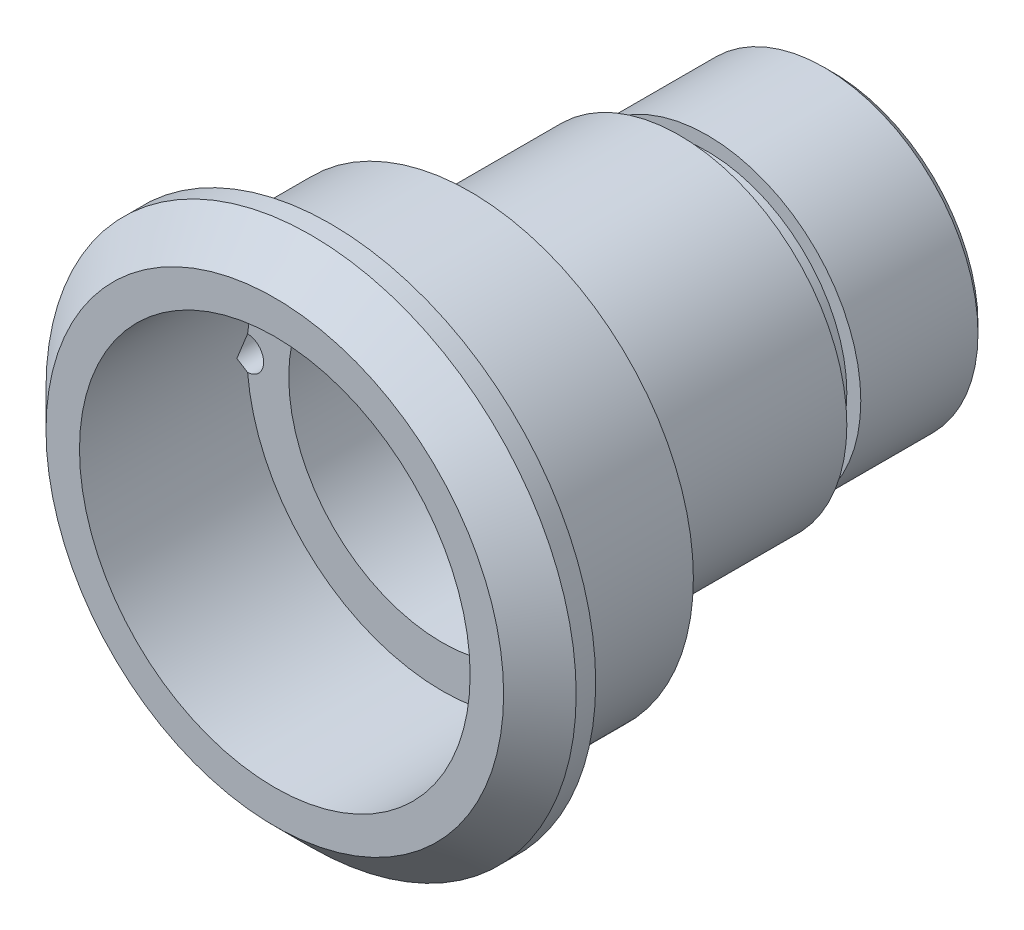
SolidWorks part; units mm, degrees
ref_plane "Front Plane" through (0, 0, 0) normal (0, 0, 1) x (1, 0, 0)
ref_plane "Top Plane" through (0, 0, 0) normal (0, 1, 0) x (1, 0, 0)
ref_plane "Right Plane" through (0, 0, 0) normal (1, 0, 0) x (0, 0, -1)
sketch "Sketch1" plane through (0, 0, 0) normal (0, 0, 1) x (1, 0, 0)
  circle A0 centre (0, 0) radius 9.5
  dimension "D1" = 19
extrude "Boss-Extrude1" add sketch "Sketch1" against normal blind 20
sketch "Sketch2" plane through (0, 0, -20) normal (0, 0, -1) x (-1, 0, 0)
  circle A0 centre (0, 0) radius 8
  dimension "D1" = 16
extrude "Cut-Extrude1" cut sketch "Sketch2" against normal offset from surface (18 mm away) 2 flip side to cut up to face at (9.5, 0, 0)
sketch "Sketch3" plane through (0, 0, -20) normal (0, 0, -1) x (-1, 0, 0)
  circle A0 centre (0, 0) radius 6
  dimension "D1" = 12
extrude "Cut-Extrude2" cut sketch "Sketch3" against normal offset from surface (13 mm away) 5 flip side to cut up to face at (9.5, 0, -2)
sketch "Sketch4" plane through (0, 0, -20) normal (0, 0, -1) x (-1, 0, 0)
  circle A0 centre (0, 0) radius 5.5
  dimension "D1" = 11
extrude "Cut-Extrude3" cut sketch "Sketch4" against normal offset from surface (5.5 mm away) 7.5 flip side to cut up to face at (8, 0, -7)
sketch "Sketch5" plane through (0, 0, 0) normal (1, 0, 0) x (0, 0, -1)
  line L0 (0, 0) -> (20, 0) construction
  line L1 (0, 9.5) -> (0, -9.5) construction
  line L2 (20, -5.5) -> (20, 5.5) construction
  line L4 (14.5, 5.5) -> (15.5, 5.5)
  line L5 (14.5, 5.5) -> (14.5, 5)
  line L6 (14.5, 5) -> (15.5, 5)
  line L7 (15.5, 5.5) -> (15.5, 5)
  dimension "D1" = 10
  dimension "D2" = 1
revolve "Cut-Revolve1" cut sketch "Sketch5" angle 360 about L0
chamfer "Chamfer1" distance 0.3 angle 45 1 edges at (-5.5, 0, -20)
chamfer "Chamfer2" distance 1.3 angle 45 1 edges at (9.5, 0, 0)
sketch "Sketch6" plane through (0, 0, 0) normal (1, 0, 0) x (0, 0, -1)
  line L0 (0, 0) -> (20, 0) construction
  line L1 (20, -5.2) -> (20, 5.2) construction
  line L2 (7, -6.433) -> (6.75, -6)
  line L3 (7, -8) -> (7, 8) construction
  line L4 (7, -6) -> (14.5, -6) construction
  line L5 (6.75, -6) -> (7, -6)
  line L6 (7, -6.433) -> (7, -6)
  dimension "D1" = 60
  dimension "D2" = 0.25
revolve "Cut-Revolve2" cut sketch "Sketch6" angle 360 about L0
sketch "Sketch7" plane through (0, 0, 0) normal (0, 0, 1) x (1, 0, 0)
  circle A0 centre (0, 0) radius 4.05
  dimension "D1" = 8.1
extrude "Cut-Extrude4" cut sketch "Sketch7" against normal through all
sketch "Sketch8" plane through (0, 0, -20) normal (0, 0, -1) x (-1, 0, 0)
  circle A0 centre (0, 0) radius 4.5
  dimension "D1" = 9
extrude "Cut-Extrude5" cut sketch "Sketch8" against normal blind 4.5
sketch "Sketch9" plane through (0, 0, -15.5) normal (0, 0, -1) x (-1, 0, 0)
  circle A0 centre (0, 0) radius 4.45
  dimension "D1" = 8.9
extrude "Cut-Extrude9" cut sketch "Sketch9" against normal offset from surface (0.2 mm away) 8.3 up to face at (6.433, 0, -7)
sketch "Sketch10" plane through (0, 0, 0) normal (0, 0, 1) x (1, 0, 0)
  circle A0 centre (0, 0) radius 7
  dimension "D1" = 14
extrude "Cut-Extrude11" cut sketch "Sketch10" against normal offset from surface (6 mm away) 1 up to face at (6.433, 0, -7)
sketch "Sketch11" plane through (0, 0, -6) normal (0, 0, 1) x (1, 0, 0)
  circle A0 centre (0, 0) radius 5.5
  dimension "D1" = 11
extrude "Cut-Extrude12" cut sketch "Sketch11" against normal offset from surface (5.6 mm away) 4.6 up to face at (6.433, 0, -7) offset beyond the face yes
sketch "Sketch12" plane through (0, 0, -11.6) normal (0, 0, 1) x (1, 0, 0)
  circle A0 centre (0, 0) radius 5.25
  dimension "D1" = 10.5
extrude "Cut-Extrude13" cut sketch "Sketch12" against normal offset from surface (1.9 mm away) 6.5 up to face at (6.433, 0, -7) offset beyond the face yes
chamfer "Chamfer3" distance 1.2 angle 45 1 edges at (4.05, 0, -13.5)
hole_wizard "Ø1.2 (1.2) Diameter Hole1" positions "Sketch16" profile "Sketch15" hole size "Ø1.2" standard "DIN"
sketch "Sketch16" plane through (0, 0, -7) normal (0, 0, -1) x (-1, 0, 0)
  circle A0 centre (0, 0) radius 7 construction
  point P0 (-7, 0)
  point P2 (7, 0)
  dimension "D1" = 14
sketch "Sketch15" plane through (7, 0, -7) normal (1, 0, 0) x (0, 1, 0)
  line L0 (0, 0) -> (0, 1.3605)
  line L1 (0, 1.3605) -> (0.6, 1)
  line L2 (0.6, 1) -> (0.6, 0)
  line L5 (0.6, 0) -> (0, 0)
  line L10 (0, 1.3605) -> (-0.6, 1) construction
  line L11 (0, -6.35) -> (0, 107.95) construction
  dimension "Hole Dia." = 1.2
  dimension "Hole Depth" = 1
  dimension "Drill Angle" = 118
